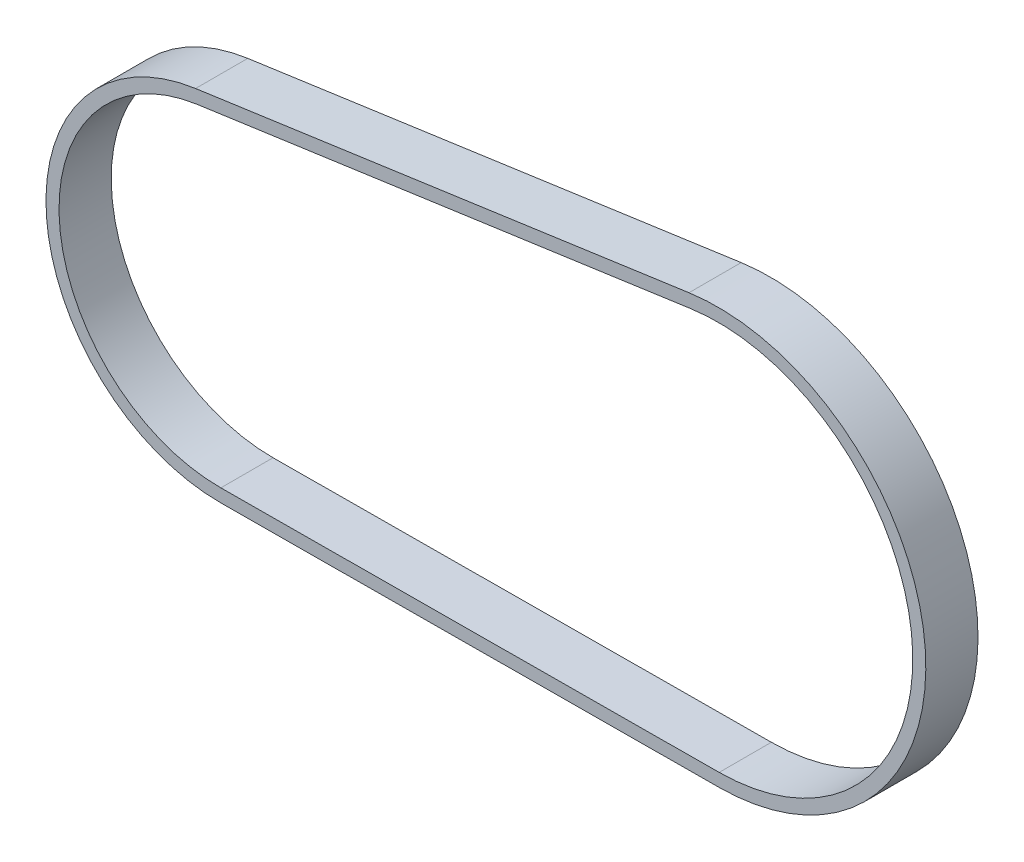
SolidWorks part; units mm, degrees
ref_plane "Front Plane" through (0, 0, 0) normal (0, 0, 1) x (1, 0, 0)
ref_plane "Top Plane" through (0, 0, 0) normal (0, 1, 0) x (1, 0, 0)
ref_plane "Right Plane" through (0, 0, 0) normal (1, 0, 0) x (0, 0, -1)
sketch "Sketch2" plane through (0, 0, 0) normal (0, 0, 1) x (1, 0, 0)
  line L0 (0, 0) -> (1, 0) construction
  line L1 (0, 0) -> (0, 1) construction
  line L6 (-2.8035, 19.8025) -> (53.9132, 27.8322)
  line L7 (57.3918, -19.6837) -> (0.1103, -19.9997)
  arc A2 (53.9132, 27.8322) -> (57.3918, -19.6837) centre (57.2601, 4.1919) cw
  arc A4 (0.1103, -19.9997) -> (-2.8035, 19.8025) centre (0, 0) cw
extrude "Extrude-Thin1" add sketch "Sketch2" against normal blind 6 thin thin type one direction reverse wall 1.5
